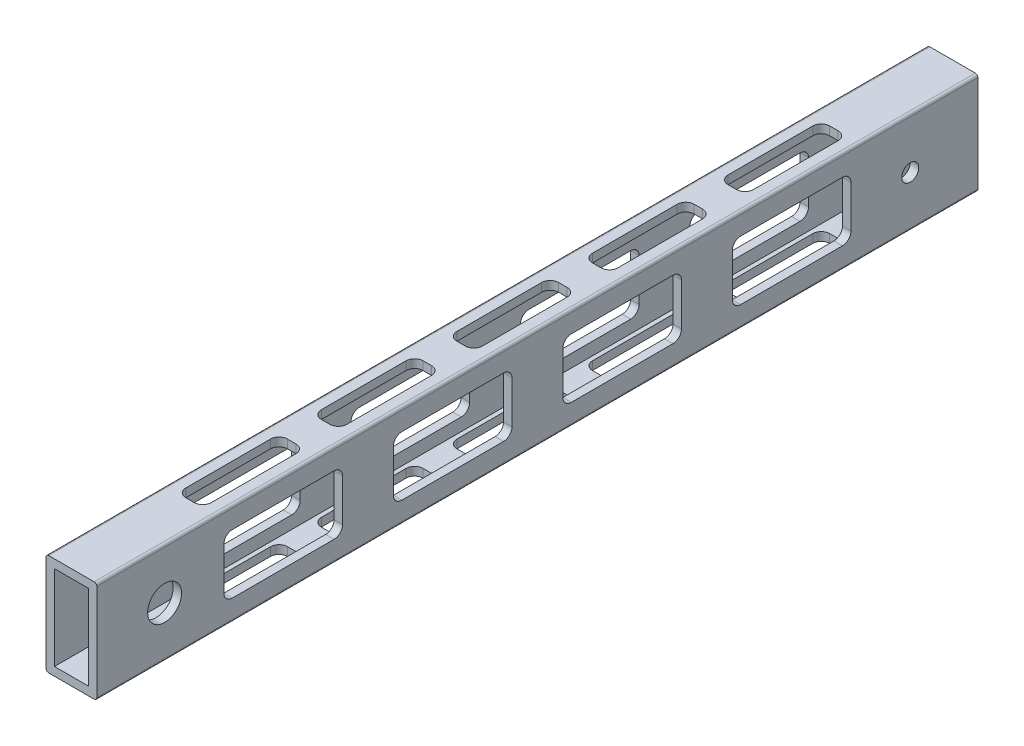
SolidWorks part; units mm, degrees
material "6061-T6 (SS)"
ref_plane "Front Plane" through (0, 0, 0) normal (0, 0, 1) x (1, 0, 0)
ref_plane "Top Plane" through (0, 0, 0) normal (0, 1, 0) x (1, 0, 0)
ref_plane "Right Plane" through (0, 0, 0) normal (1, 0, 0) x (0, 0, -1)
sketch "Sketch1" plane through (0, 0, 0) normal (0, 0, 1) x (1, 0, 0)
  line L0 (-6.35, -15.875) -> (-6.35, 15.875)
  line L1 (-8.525, -19.05) -> (8.525, -19.05)
  line L2 (-9.525, -18.05) -> (-9.525, 18.05)
  line L3 (-8.525, 19.05) -> (8.525, 19.05)
  line L4 (9.525, -18.05) -> (9.525, 18.05)
  line L5 (-9.525, -19.05) -> (9.525, 19.05) construction
  line L6 (-9.525, 19.05) -> (9.525, -19.05) construction
  line L7 (-6.35, 15.875) -> (6.35, 15.875)
  line L8 (6.35, -15.875) -> (6.35, 15.875)
  line L9 (-6.35, -15.875) -> (6.35, -15.875)
  arc A0 (-8.525, -19.05) -> (-9.525, -18.05) centre (-8.525, -18.05) cw
  arc A1 (8.525, -19.05) -> (9.525, -18.05) centre (8.525, -18.05) ccw
  arc A2 (8.525, 19.05) -> (9.525, 18.05) centre (8.525, 18.05) cw
  arc A3 (-9.525, 18.05) -> (-8.525, 19.05) centre (-8.525, 18.05) cw
  arc A4 (-6.35, 15.875) -> (-6.35, 15.875) centre (-6.35, 15.875) cw
  arc A5 (6.35, 15.875) -> (6.35, 15.875) centre (6.35, 15.875) cw
  arc A6 (6.35, -15.875) -> (6.35, -15.875) centre (6.35, -15.875) ccw
  arc A7 (-6.35, -15.875) -> (-6.35, -15.875) centre (-6.35, -15.875) cw
  point P0 (0, 0)
  dimension "D3" = 1
  dimension "D1" = 19.05
  dimension "D2" = 38.1
  dimension "D4" = 3.175
extrude "Boss-Extrude1" add sketch "Sketch1" along normal mid plane 330.2
sketch "Sketch2" plane through (0, 19.05, 0) normal (0, 1, 0) x (1, 0, 0)
  line L0 (-4.7625, -66.675) -> (-4.7625, -34.925)
  line L1 (-1.5875, -120.65) -> (1.5875, -120.65)
  line L2 (-4.7625, -117.475) -> (-4.7625, -85.725)
  line L3 (-1.5875, -82.55) -> (1.5875, -82.55)
  line L4 (4.7625, -117.475) -> (4.7625, -85.725)
  line L5 (-4.7625, -120.65) -> (4.7625, -82.55) construction
  line L6 (-4.7625, -82.55) -> (4.7625, -120.65) construction
  line L7 (-1.5875, -69.85) -> (1.5875, -69.85)
  line L8 (4.7625, -66.675) -> (4.7625, -34.925)
  line L9 (-1.5875, -31.75) -> (1.5875, -31.75)
  line L10 (-4.7625, -15.875) -> (-4.7625, 15.875)
  line L11 (-1.5875, -19.05) -> (1.5875, -19.05)
  line L12 (4.7625, -15.875) -> (4.7625, 15.875)
  line L13 (-1.5875, 19.05) -> (1.5875, 19.05)
  line L14 (-4.7625, 34.925) -> (-4.7625, 66.675)
  line L15 (-1.5875, 31.75) -> (1.5875, 31.75)
  line L16 (4.7625, 34.925) -> (4.7625, 66.675)
  line L17 (-1.5875, 69.85) -> (1.5875, 69.85)
  line L18 (-4.7625, 85.725) -> (-4.7625, 117.475)
  line L19 (-1.5875, 82.55) -> (1.5875, 82.55)
  line L20 (4.7625, 85.725) -> (4.7625, 117.475)
  line L21 (-1.5875, 120.65) -> (1.5875, 120.65)
  line L22 (0, -101.6) -> (0, -50.8) construction
  arc A0 (-1.5875, -120.65) -> (-4.7625, -117.475) centre (-1.5875, -117.475) cw
  arc A1 (1.5875, -120.65) -> (4.7625, -117.475) centre (1.5875, -117.475) ccw
  arc A2 (1.5875, -82.55) -> (4.7625, -85.725) centre (1.5875, -85.725) cw
  arc A3 (-4.7625, -85.725) -> (-1.5875, -82.55) centre (-1.5875, -85.725) cw
  arc A4 (-4.7625, -34.925) -> (-1.5875, -31.75) centre (-1.5875, -34.925) cw
  arc A5 (-1.5875, -69.85) -> (-4.7625, -66.675) centre (-1.5875, -66.675) cw
  arc A6 (1.5875, -69.85) -> (4.7625, -66.675) centre (1.5875, -66.675) ccw
  arc A7 (1.5875, -31.75) -> (4.7625, -34.925) centre (1.5875, -34.925) cw
  arc A8 (-4.7625, 15.875) -> (-1.5875, 19.05) centre (-1.5875, 15.875) cw
  arc A9 (-1.5875, -19.05) -> (-4.7625, -15.875) centre (-1.5875, -15.875) cw
  arc A10 (1.5875, -19.05) -> (4.7625, -15.875) centre (1.5875, -15.875) ccw
  arc A11 (1.5875, 19.05) -> (4.7625, 15.875) centre (1.5875, 15.875) cw
  arc A12 (-4.7625, 66.675) -> (-1.5875, 69.85) centre (-1.5875, 66.675) cw
  arc A13 (-1.5875, 31.75) -> (-4.7625, 34.925) centre (-1.5875, 34.925) cw
  arc A14 (1.5875, 31.75) -> (4.7625, 34.925) centre (1.5875, 34.925) ccw
  arc A15 (1.5875, 69.85) -> (4.7625, 66.675) centre (1.5875, 66.675) cw
  arc A16 (-4.7625, 117.475) -> (-1.5875, 120.65) centre (-1.5875, 117.475) cw
  arc A17 (-1.5875, 82.55) -> (-4.7625, 85.725) centre (-1.5875, 85.725) cw
  arc A18 (1.5875, 82.55) -> (4.7625, 85.725) centre (1.5875, 85.725) ccw
  arc A19 (1.5875, 120.65) -> (4.7625, 117.475) centre (1.5875, 117.475) cw
  point P0 (0, -101.6)
  point P5 (0, 0)
  point P19 (0, 0)
  point P20 (0, -50.8)
  point P33 (0, 0)
  point P46 (0, 50.8)
  point P59 (0, 101.6)
  dimension "D3" = 3.175
  dimension "D1" = 9.525
  dimension "D2" = 38.1
  dimension "D5" = 50.8
  dimension "D4" = 5
extrude "Cut-Extrude1" cut sketch "Sketch2" against normal through all both and the other way through all
sketch "Sketch3" plane through (9.525, 0, 0) normal (1, 0, 0) x (0, 0, -1)
  line L0 (-53.975, -7.9375) -> (-53.975, 7.9375)
  line L1 (-114.3, -11.1125) -> (-76.2, -11.1125)
  line L2 (-117.475, -7.9375) -> (-117.475, 7.9375)
  line L3 (-114.3, 11.1125) -> (-76.2, 11.1125)
  line L4 (-73.025, -7.9375) -> (-73.025, 7.9375)
  line L5 (-117.475, -11.1125) -> (-73.025, 11.1125) construction
  line L6 (-117.475, 11.1125) -> (-73.025, -11.1125) construction
  line L7 (-50.8, -11.1125) -> (-12.7, -11.1125)
  line L8 (-9.525, -7.9375) -> (-9.525, 7.9375)
  line L9 (-50.8, 11.1125) -> (-12.7, 11.1125)
  line L10 (9.525, -7.9375) -> (9.525, 7.9375)
  line L11 (12.7, -11.1125) -> (50.8, -11.1125)
  line L12 (53.975, -7.9375) -> (53.975, 7.9375)
  line L13 (12.7, 11.1125) -> (50.8, 11.1125)
  line L14 (-95.25, 0) -> (-31.75, 0) construction
  line L15 (73.025, -7.9375) -> (73.025, 7.9375)
  line L16 (76.2, -11.1125) -> (114.3, -11.1125)
  line L17 (117.475, -7.9375) -> (117.475, 7.9375)
  line L18 (76.2, 11.1125) -> (114.3, 11.1125)
  line L19 (31.75, 0) -> (95.25, 0) construction
  line L28 (-31.75, 0) -> (31.75, 0) construction
  arc A0 (-114.3, -11.1125) -> (-117.475, -7.9375) centre (-114.3, -7.9375) cw
  arc A1 (-76.2, -11.1125) -> (-73.025, -7.9375) centre (-76.2, -7.9375) ccw
  arc A2 (-76.2, 11.1125) -> (-73.025, 7.9375) centre (-76.2, 7.9375) cw
  arc A3 (-117.475, 7.9375) -> (-114.3, 11.1125) centre (-114.3, 7.9375) cw
  arc A4 (-53.975, 7.9375) -> (-50.8, 11.1125) centre (-50.8, 7.9375) cw
  arc A5 (-50.8, -11.1125) -> (-53.975, -7.9375) centre (-50.8, -7.9375) cw
  arc A6 (-12.7, -11.1125) -> (-9.525, -7.9375) centre (-12.7, -7.9375) ccw
  arc A7 (-12.7, 11.1125) -> (-9.525, 7.9375) centre (-12.7, 7.9375) cw
  arc A8 (9.525, 7.9375) -> (12.7, 11.1125) centre (12.7, 7.9375) cw
  arc A9 (12.7, -11.1125) -> (9.525, -7.9375) centre (12.7, -7.9375) cw
  arc A10 (50.8, -11.1125) -> (53.975, -7.9375) centre (50.8, -7.9375) ccw
  arc A11 (50.8, 11.1125) -> (53.975, 7.9375) centre (50.8, 7.9375) cw
  arc A12 (73.025, 7.9375) -> (76.2, 11.1125) centre (76.2, 7.9375) cw
  arc A13 (76.2, -11.1125) -> (73.025, -7.9375) centre (76.2, -7.9375) cw
  arc A14 (114.3, -11.1125) -> (117.475, -7.9375) centre (114.3, -7.9375) ccw
  arc A15 (114.3, 11.1125) -> (117.475, 7.9375) centre (114.3, 7.9375) cw
  point P0 (-95.25, 0)
  point P19 (95.25, 0)
  point P20 (-31.75, 0)
  point P33 (31.75, 0)
  point P60 (0, 0)
  dimension "D3" = 3.175
  dimension "D1" = 22.225
  dimension "D2" = 44.45
  dimension "D5" = 63.5
  dimension "D4" = 4
extrude "Cut-Extrude2" cut sketch "Sketch3" against normal through all both and the other way through all
sketch "Sketch4" plane through (9.525, 0, 0) normal (1, 0, 0) x (0, 0, -1)
  line L0 (-165.1, -18.05) -> (-165.1, 18.05) construction
  line L2 (-139.7, 0) -> (-165.1, 0) construction
  line L3 (-139.7, 0) -> (-139.7, 19.05) construction
  line L4 (165.1, 0) -> (139.7, 0) construction
  line L5 (165.1, -18.05) -> (165.1, 18.05) construction
  line L6 (139.7, 0) -> (139.7, 19.05) construction
  line L7 (-165.1, 19.05) -> (165.1, 19.05) construction
  circle A0 centre (-139.7, 0) radius 6.35
  circle A1 centre (139.7, 0) radius 3.175
  point P10 (0, 0)
  point P15 (139.7, 0)
  dimension "D1" = 12.7
  dimension "D4" = 6.35
  dimension "D2" = 19.05
  dimension "D3" = 25.4
extrude "Cut-Extrude3" cut sketch "Sketch4" against normal through all both and the other way through all
